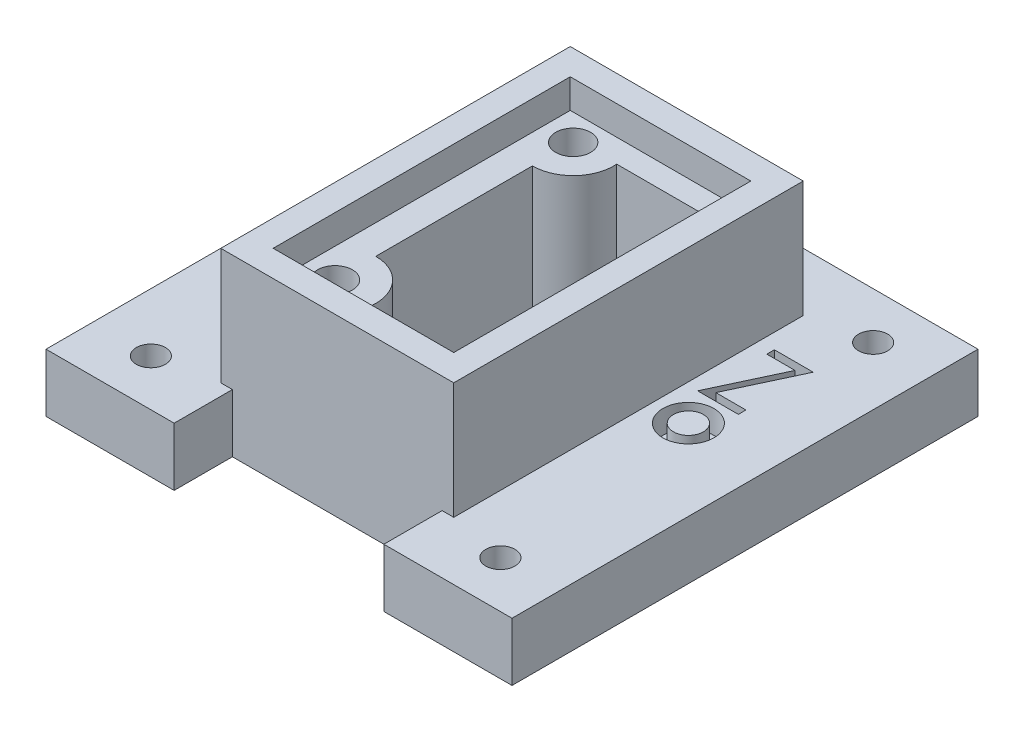
SolidWorks part; units mm, degrees
ref_plane "Front" through (0, 0, 0) normal (0, 0, 1) x (1, 0, 0)
ref_plane "Top" through (0, 0, 0) normal (0, 1, 0) x (1, 0, 0)
ref_plane "Right" through (0, 0, 0) normal (1, 0, 0) x (0, 0, -1)
sketch "Sketch1" plane through (0, 0, 0) normal (0, 1, 0) x (1, 0, 0)
  line L0 (-8.0987, 18.7927) -> (-8.0987, -52.9321) construction
  line L1 (-28.0987, 18.7927) -> (11.9013, 18.7927)
  line L2 (-28.0987, 18.7927) -> (-28.0987, -21.2073)
  line L3 (-28.0987, -21.2073) -> (-17.0987, -21.2073)
  line L4 (11.9013, 18.7927) -> (11.9013, -21.2073)
  line L5 (-28.0987, -1.2073) -> (21.4934, -1.2073) construction
  line L6 (-39.8723, -16.2073) -> (21.4934, -16.2073) construction
  line L7 (-17.0987, -21.2073) -> (-17.0987, -16.2073)
  line L8 (-17.0987, -16.2073) -> (0.9013, -16.2073)
  line L9 (0.9013, -21.2073) -> (0.9013, -16.2073)
  line L10 (0.9013, -21.2073) -> (11.9013, -21.2073)
  point P14 (-8.0987, -16.2073)
  dimension "D1" = 40
  dimension "D2" = 40
  dimension "D3" = 5
  dimension "D4" = 9
extrude "Boss-Extrude1" add sketch "Sketch1" along normal blind 5
sketch "Sketch2" plane through (0, 5, 0) normal (0, 1, 0) x (1, 0, 0)
  line L0 (-8.0987, 18.7927) -> (-8.0987, -31.7546) construction
  line L1 (11.9013, 18.7927) -> (-28.0987, 18.7927) construction
  line L2 (-28.0987, -1.2073) -> (20.4926, -1.2073) construction
  line L3 (-28.0987, 18.7927) -> (-28.0987, -21.2073) construction
  line L5 (-18.0987, 13.7927) -> (1.9013, 13.7927)
  line L6 (-18.0987, 13.7927) -> (-18.0987, -16.2073)
  line L7 (-18.0987, -16.2073) -> (1.9013, -16.2073)
  line L8 (1.9013, 13.7927) -> (1.9013, -16.2073)
  dimension "D1" = 20
  dimension "D2" = 30
  dimension "D3" = 10
  dimension "D4" = 15
extrude "Boss-Extrude2" add sketch "Sketch2" along normal blind 10
sketch "Sketch3" plane through (0, 15, 0) normal (0, 1, 0) x (1, 0, 0)
  line L0 (-18.0987, -1.2073) -> (10.7494, -1.2073) construction
  line L1 (-18.0987, 13.7927) -> (-18.0987, -16.2073) construction
  line L2 (-8.0987, 13.7927) -> (-8.0987, -18.2398) construction
  line L3 (1.9013, 13.7927) -> (-18.0987, 13.7927) construction
  line L6 (-15.8487, 11.5427) -> (-0.3487, 11.5427)
  line L7 (-15.8487, 11.5427) -> (-15.8487, -13.9573)
  line L8 (-15.8487, -13.9573) -> (-0.3487, -13.9573)
  line L9 (-0.3487, 11.5427) -> (-0.3487, -13.9573)
  dimension "D1" = 15.5
  dimension "D2" = 25.5
  dimension "D3" = 12.75
  dimension "D4" = 7.75
extrude "Cut-Extrude1" cut sketch "Sketch3" against normal blind 2.5
sketch "Sketch4" plane through (0, 12.5, 0) normal (0, 1, 0) x (1, 0, 0)
  line L0 (-15.8487, -13.9573) -> (-0.3487, -13.9573) construction
  line L1 (-15.8487, 11.5427) -> (-15.8487, -13.9573) construction
  line L2 (-9.8577, 9.5427) -> (-2.8487, 9.5427)
  line L3 (-0.3487, -13.9573) -> (-0.3487, 11.5427) construction
  line L4 (-13.3487, 9.2927) -> (-13.3487, -21.7863) construction
  line L5 (-4.295, -11.4573) -> (-31.4682, -11.4573) construction
  line L9 (-2.8487, 9.5427) -> (-2.8487, -11.4573)
  line L10 (-2.8487, -11.4573) -> (-9.8622, -11.4573)
  line L11 (-13.3487, -7.6509) -> (-13.3487, 5.7927)
  circle A1 centre (-13.3487, -11.1509) radius 3.5 construction
  circle A2 centre (-13.3487, 9.2927) radius 1.5
  circle A3 centre (-13.3487, -11.1509) radius 1.5
  arc A4 (-13.3487, 5.7927) -> (-9.8577, 9.5427) centre (-13.3487, 9.2927) ccw
  arc A5 (-9.8622, -11.4573) -> (-13.3487, -7.6509) centre (-13.3487, -11.1509) ccw
  circle A7 centre (-13.3487, 9.2927) radius 3.5 construction
  point P1 (1.9201, 13.7901)
  point P2 (-13.0799, -11.2099)
  point P6 (1.9201, -11.2099)
  point P10 (-13.0799, 13.7901)
  point P13 (-11.0799, 11.7901)
  point P16 (-11.0799, -9.2099)
  point P17 (-7.5799, 11.5401)
  point P19 (-7.5799, -8.9599)
  dimension "D3" = 3
  dimension "D6" = 3
  dimension "D1" = 2.5
  dimension "D2" = 2.5
  dimension "D4" = 2.5
  dimension "D9" = 2
extrude "Cut-Extrude2" cut sketch "Sketch4" against normal up to surface (12.5 mm away) up to face at (-8.0987, 0, 9.9573)
sketch "Sketch5" plane through (0, 0, 0) normal (0, -1, 0) x (1, 0, 0)
  line L1 (-10.7228, 9.5799) -> (-10.6752, 12.6395)
  line L2 (-10.6752, 12.6395) -> (-13.3011, 14.2105)
  line L3 (-13.3011, 14.2105) -> (-15.9746, 12.7218)
  line L4 (-15.9746, 12.7218) -> (-16.0222, 9.6623)
  line L5 (-16.0222, 9.6623) -> (-13.3963, 8.0913)
  line L6 (-13.3963, 8.0913) -> (-10.7228, 9.5799)
  line L7 (-10.3064, -9.6207) -> (-11.5434, -6.822)
  line L8 (-11.5434, -6.822) -> (-14.5857, -6.4939)
  line L9 (-14.5857, -6.4939) -> (-16.391, -8.9646)
  line L10 (-16.391, -8.9646) -> (-15.154, -11.7633)
  line L11 (-15.154, -11.7633) -> (-12.1117, -12.0914)
  line L12 (-12.1117, -12.0914) -> (-10.3064, -9.6207)
  circle A0 centre (-13.3487, 11.1509) radius 2.65 construction
  circle A1 centre (-13.3487, -9.2927) radius 2.65 construction
  dimension "D1" = 5.3
  dimension "D2" = 5.3
extrude "Cut-Extrude3" cut sketch "Sketch5" against normal blind 2.5
sketch "Sketch10" plane through (0, 5, 0) normal (0, 1, 0) x (1, 0, 0)
  line L2 (1.9013, 13.7927) -> (-18.0987, 13.7927) construction
  line L3 (-17.9386, 3.2714) -> (-23.2666, 3.2714) construction
  line L4 (-17.9386, -4.5372) -> (-17.9386, 7.2326) construction
  line L5 (-23.2666, -4.5372) -> (-23.2666, 7.5813) construction
  circle A0 centre (4.9717, 0.864) radius 2.1872
  circle A2 centre (4.9717, 0.864) radius 1.286
  text T0 "X" font "Century Gothic" height in points 18
  text T1 "k" font "SWAstro" height 6.35
  text T2 "Y"
  text T3 "l" font "SWAstro" height 6.35
  text T4 "Z"
extrude "Cut-Extrude7" cut sketch "Sketch10" against normal blind 2
sketch "Sketch11" plane through (0, 5, 0) normal (0, 1, 0) x (1, 0, 0)
  line L0 (-8.0987, 18.7927) -> (-8.0987, -21.2073) construction
  line L1 (11.9013, 18.7927) -> (-28.0987, 18.7927) construction
  line L3 (-28.0987, -1.2073) -> (11.9013, -1.2073) construction
  line L4 (-28.0987, 18.7927) -> (-28.0987, -21.2073) construction
  line L5 (11.9013, -21.2073) -> (11.9013, 18.7927) construction
  circle A0 centre (-23.0987, 14.7927) radius 1.25
  circle A1 centre (6.9013, 14.7927) radius 1.25
  circle A2 centre (6.9013, -17.2073) radius 1.25
  circle A3 centre (-23.0987, -17.2073) radius 1.25
  dimension "D1" = 2.5
  dimension "D2" = 4
  dimension "D3" = 5
extrude "Cut-Extrude8" cut sketch "Sketch11" against normal up to surface (5 mm away) up to face at (-13.3487, 0, -9.2927)
